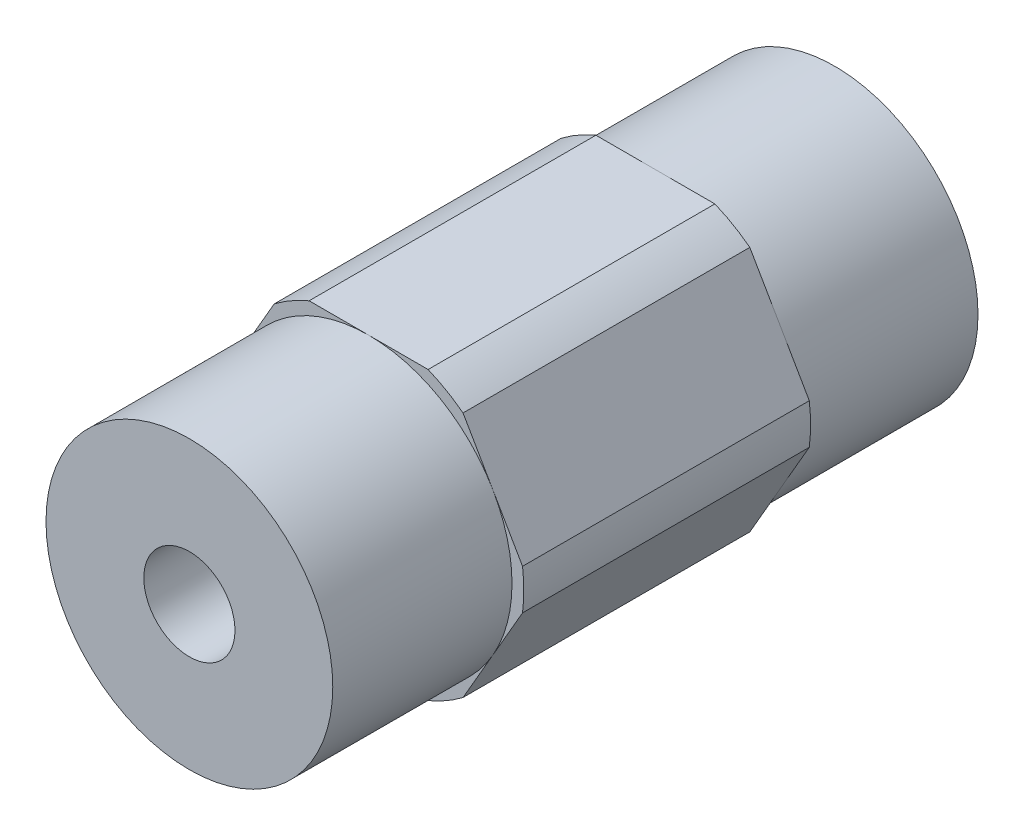
SolidWorks part; units mm, degrees
material "7075-T6 (SN)"
ref_plane "Front Plane" through (0, 0, 0) normal (0, 0, 1) x (1, 0, 0)
ref_plane "Top Plane" through (0, 0, 0) normal (0, 1, 0) x (1, 0, 0)
ref_plane "Right Plane" through (0, 0, 0) normal (1, 0, 0) x (0, 0, -1)
sketch "Sketch1" plane through (0, 0, 0) normal (0, 0, 1) x (1, 0, 0)
  line L1 (7.3323, 0) -> (3.6662, 6.35)
  line L2 (3.6662, 6.35) -> (-3.6662, 6.35)
  line L3 (-3.6662, 6.35) -> (-7.3323, 0)
  line L4 (-7.3323, 0) -> (-3.6662, -6.35)
  line L5 (-3.6662, -6.35) -> (3.6662, -6.35)
  line L6 (3.6662, -6.35) -> (7.3323, 0)
  circle A0 centre (0, 0) radius 6.35 construction
  circle A1 centre (0, 0) radius 2.0193
  circle A2 centre (0, 0) radius 6.875
  dimension "D1" = 12.7
  dimension "D2" = 4.0386
  dimension "D3" = 13.75
extrude "Boss-Extrude1" add sketch "Sketch1" along normal mid plane 28.575 contours L1 A2 L2 L3 L4 L5 L6 A1 region at (6.6736, 0.4353, 0)
hole_wizard "#10-32 Tapped Hole1" positions "3DSketch1" profile "Sketch3" tap size "#10-32" standard "ANSI Inch"
sketch3d "3DSketch1"
  circle A0 centre (0, 0, -14.2875) radius 2.0193 construction
  circle A1 centre (0, 0, 14.2875) radius 2.0193 construction
  point P0 (0, 0, 14.2875)
  point P2 (0, 0, -14.2875)
  point P6 (0, 0, -12.2682)
  point P9 (0, 0, 16.3068)
sketch "Sketch3" plane through (0, 0, 14.2875) normal (1, 0, 0) x (0, -1, 0)
  line L0 (0, 0) -> (0, 13.1513)
  line L1 (0, 13.1513) -> (2.0193, 11.938)
  line L2 (2.0193, 11.938) -> (2.0193, 0)
  line L5 (2.0193, 0) -> (0, 0)
  line L10 (0, 13.1513) -> (-2.0193, 11.938) construction
  line L11 (0, -6.35) -> (0, 107.95) construction
  dimension "Tap Drill Dia." = 4.0386
  dimension "Tap Drill Depth" = 11.938
  dimension "Drill Angle" = 118
cosmetic thread "Hole Thread1" parameters "D1"=9.652, "D2"=4.826
cosmetic thread "Hole Thread2" parameters "D1"=9.652, "D2"=4.826
sketch "Sketch4" plane through (0, 0, 14.2875) normal (0, 0, 1) x (1, 0, 0)
  circle A0 centre (0, 0) radius 6.35
  dimension "D1" = 12.7
extrude "Cut-Extrude-Thin1" cut sketch "Sketch4" against normal blind 7.9375 thin thin type one direction wall 2.54
mirror "Mirror1" about plane through (0, 0, 0) normal (0, 0, 1) of "Cut-Extrude-Thin1"
equation "\"D3@Sketch1\"=13.75mm"
